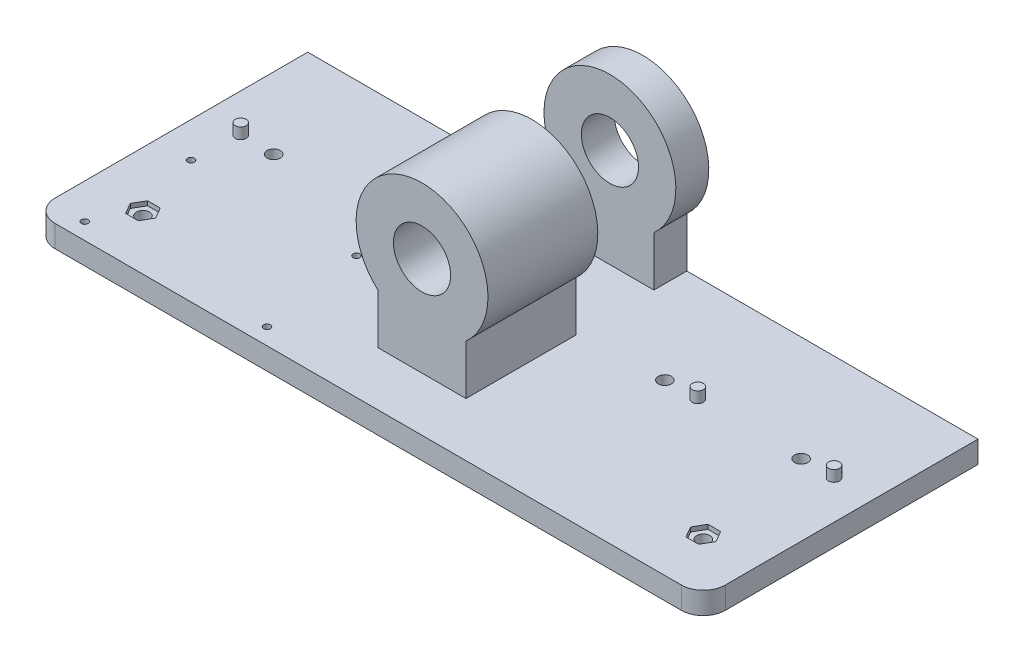
SolidWorks part; units mm, degrees
ref_plane "Front Plane" through (0, 0, 0) normal (0, 0, 1) x (1, 0, 0)
ref_plane "Top Plane" through (0, 0, 0) normal (0, 1, 0) x (1, 0, 0)
ref_plane "Right Plane" through (0, 0, 0) normal (1, 0, 0) x (0, 0, -1)
sketch "Sketch1" plane through (0, 0, 0) normal (0, 1, 0) x (1, 0, 0)
  line L0 (152.5, 125) -> (152.5, 0) construction
  line L1 (0, 0) -> (305, 0)
  line L2 (0, 0) -> (0, 125)
  line L3 (0, 125) -> (305, 125)
  line L4 (305, 0) -> (305, 125)
  line L5 (25, 100) -> (280, 100) construction
  line L6 (280, 25) -> (280, 100) construction
  line L7 (25, 25) -> (280, 25) construction
  line L8 (25, 25) -> (25, 100) construction
  line L9 (152.5, 62.5) -> (25, 62.5) construction
  line L10 (30.7735, 100) -> (27.8868, 105) construction
  line L11 (27.8868, 105) -> (22.1132, 105) construction
  line L12 (22.1132, 105) -> (19.2265, 100) construction
  line L13 (19.2265, 100) -> (22.1132, 95) construction
  line L14 (22.1132, 95) -> (27.8868, 95) construction
  line L15 (27.8868, 95) -> (30.7735, 100) construction
  line L16 (27.8868, 30) -> (30.7735, 25) construction
  line L17 (22.1132, 30) -> (27.8868, 30) construction
  line L18 (19.2265, 25) -> (22.1132, 30) construction
  line L19 (22.1132, 20) -> (19.2265, 25) construction
  line L20 (27.8868, 20) -> (22.1132, 20) construction
  line L21 (30.7735, 25) -> (27.8868, 20) construction
  line L22 (282.8868, 30) -> (277.1132, 30) construction
  line L23 (285.7735, 25) -> (282.8868, 30) construction
  line L24 (282.8868, 20) -> (285.7735, 25) construction
  line L25 (277.1132, 20) -> (282.8868, 20) construction
  line L26 (274.2265, 25) -> (277.1132, 20) construction
  line L27 (277.1132, 30) -> (274.2265, 25) construction
  line L28 (277.1132, 95) -> (274.2265, 100) construction
  line L29 (282.8868, 95) -> (277.1132, 95) construction
  line L30 (285.7735, 100) -> (282.8868, 95) construction
  line L31 (282.8868, 105) -> (285.7735, 100) construction
  line L32 (277.1132, 105) -> (282.8868, 105) construction
  line L33 (274.2265, 100) -> (277.1132, 105) construction
  line L34 (172.5, 75) -> (172.5, 125) construction
  line L35 (132.5, 0) -> (172.5, 0) construction
  line L36 (132.5, 0) -> (132.5, 125) construction
  line L37 (132.5, 125) -> (172.5, 125) construction
  line L38 (172.5, 0) -> (172.5, 125) construction
  line L40 (132.5, 75) -> (132.5, 25) construction
  line L41 (132.5, 25) -> (172.5, 25) construction
  line L42 (172.5, 75) -> (172.5, 25) construction
  line L50 (305, 14.5) -> (253.3, 14.5) construction
  line L51 (10, 69.5) -> (10, 84.5) construction
  line L52 (10, 69.5) -> (40, 69.5) construction
  line L53 (10, 84.5) -> (25, 69.5) construction
  line L54 (0, 125) -> (108, 125) construction
  line L55 (0, 125) -> (0, 84.5) construction
  line L56 (0, 84.5) -> (108, 84.5) construction
  line L57 (108, 125) -> (108, 84.5) construction
  line L58 (25, 69.5) -> (25, 84.5) construction
  line L59 (40, 84.5) -> (0, 84.5) construction
  line L60 (40, 84.5) -> (40, 69.5) construction
  line L62 (0, 84.5) -> (0, 69.5) construction
  line L63 (102, 84.5) -> (102, 69.5) construction
  line L64 (62, 0) -> (62, 125) construction
  line L65 (253.3, 14.5) -> (253.3, 0) construction
  line L67 (253.3, 14.5) -> (280.2, 14.5) construction
  circle A1 centre (25, 100) radius 5 construction
  circle A3 centre (280, 25) radius 3
  circle A4 centre (25, 25) radius 3
  circle A10 centre (17.5, 77) radius 3 construction
  circle A11 centre (32.5, 77) radius 3
  circle A12 centre (79.5, 77) radius 3 construction
  circle A13 centre (94.5, 77) radius 3
  circle A14 centre (210.5, 77) radius 3
  circle A15 centre (225.5, 77) radius 3 construction
  circle A16 centre (272.5, 77) radius 3
  circle A17 centre (287.5, 77) radius 3 construction
  point P54 (25, 69.5)
  point P56 (0, 0)
  point P57 (17.5, 77)
  dimension "D3" = 6
  dimension "D1" = 305
  dimension "D2" = 125
  dimension "D5" = 10
  dimension "D6" = 40
  dimension "D7" = 40.5
  dimension "D9" = 108
  dimension "D15" = 62
  dimension "D18" = 51.7
  dimension "D19" = 14.5
  dimension "D20" = 26.9
  dimension "D8" = 40
  dimension "D11" = 30
  dimension "D10" = 15
  dimension "D4" = 25
  dimension "D14" = 2
extrude "Boss-Extrude1" add sketch "Sketch1" along normal blind 10
sketch "Sketch7" plane through (0, 10, 0) normal (0, 1, 0) x (1, 0, 0)
  line L0 (0, 0) -> (305, 0) construction
  line L1 (132.5, 24.5) -> (172.5, 24.5)
  line L2 (132.5, 24.5) -> (132.5, 74.5)
  line L3 (132.5, 74.5) -> (172.5, 74.5)
  line L4 (172.5, 24.5) -> (172.5, 74.5)
  line L5 (152.5, 0) -> (152.5, 125) construction
  line L6 (305, 125) -> (0, 125) construction
  line L18 (132.5, 110) -> (172.5, 110)
  line L19 (132.5, 110) -> (132.5, 125)
  line L20 (132.5, 125) -> (172.5, 125)
  line L21 (172.5, 110) -> (172.5, 125)
  point P11 (152.5, 74.5)
  point P20 (152.5, 110)
  dimension "D1" = 40
  dimension "D2" = 50
  dimension "D4" = 15
  dimension "D3" = 35.5
extrude "Boss-Extrude2" add sketch "Sketch7" along normal blind 22.6393
sketch "Sketch11" plane through (0, 0, -24.5) normal (0, 0, 1) x (1, 0, 0)
  circle A0 centre (152.5, 55) radius 30
  circle A1 centre (152.5, 55) radius 13
  dimension "D1" = 60
  dimension "D2" = 26
extrude "Boss-Extrude3" add sketch "Sketch11" against normal up to surface (100.5 mm away) up to face at (152.5, 13.1598, -125)
ref_plane "Plane1" through (0, 0, -62.5) normal (0, 0, 1) x (1, 0, 0)
sketch "Sketch12" plane through (305, 0, 0) normal (1, 0, 0) x (0, 0, -1)
  line L0 (125, 85) -> (24.5, 85) construction
  line L1 (74.5, 10) -> (110, 10)
  line L2 (74.5, 10) -> (74.5, 85)
  line L3 (74.5, 85) -> (110, 85)
  line L4 (110, 10) -> (110, 85)
  line L6 (110, 32.6393) -> (110, 10) construction
extrude "Cut-Extrude2" cut sketch "Sketch12" against normal through all
sketch "Sketch6" plane through (0, 10, 0) normal (0, 1, 0) x (1, 0, 0)
  line L0 (152.5, 125) -> (152.5, 0) construction
  line L8 (0, 0) -> (305, 0) construction
  line L9 (152.5, 62.5) -> (0, 62.5) construction
  line L10 (0, 125) -> (0, 0) construction
  line L29 (27.8868, 30) -> (30.7735, 25)
  line L30 (274.2265, 25) -> (277.1132, 20)
  line L31 (277.1132, 20) -> (282.8868, 20)
  line L32 (282.8868, 20) -> (285.7735, 25)
  line L33 (285.7735, 25) -> (282.8868, 30)
  line L34 (282.8868, 30) -> (277.1132, 30)
  line L35 (277.1132, 30) -> (274.2265, 25)
  line L36 (22.1132, 30) -> (27.8868, 30)
  line L37 (19.2265, 25) -> (22.1132, 30)
  line L38 (22.1132, 20) -> (19.2265, 25)
  line L39 (27.8868, 20) -> (22.1132, 20)
  line L40 (30.7735, 25) -> (27.8868, 20)
  circle A0 centre (280, 25) radius 5 construction
  dimension "D1" = 10
extrude "Cut-Extrude1" cut sketch "Sketch6" against normal blind 2
sketch "Sketch15" plane through (0, 10, 0) normal (0, 1, 0) x (1, 0, 0)
  line L0 (79.5, 77) -> (17.5, 77) construction
  line L1 (48.5, 77) -> (48.5, 84.5) construction
  line L2 (0, 84.5) -> (108, 84.5) construction
  line L3 (152.5, 125) -> (152.5, 0) construction
  circle A1 centre (79.5, 77) radius 2.5
  circle A2 centre (17.5, 77) radius 2.5
  circle A3 centre (17.5, 77) radius 2.5
  circle A4 centre (225.5, 77) radius 2.5
  circle A5 centre (287.5, 77) radius 2.5
  dimension "D1" = 0.5
extrude "Boss-Extrude5" add sketch "Sketch15" along normal blind 5
sketch "Sketch16" plane through (0, 10, 0) normal (0, 1, 0) x (1, 0, 0)
  line L0 (0, 0) -> (305, 0) construction
  line L1 (0, 125) -> (0, 0) construction
  circle A0 centre (16, 7.5) radius 1.55
  circle A1 centre (98.95, 7.5) radius 1.55
  circle A2 centre (16, 55.866) radius 1.55
  circle A3 centre (91.33, 55.866) radius 1.55
  dimension "D1" = 3.1
  dimension "D2" = 7.5
  dimension "D3" = 82.95
  dimension "D4" = 16
  dimension "D5" = 48.366
  dimension "D6" = 75.33
extrude "Cut-Extrude3" cut sketch "Sketch16" against normal through all
chamfer "Chamfer1" distance 3.3 angle 45 4 edges at (272.5, 0, -74) (210.5, 0, -74) (94.5, 0, -80) (32.5, 0, -80)
fillet "Fillet3" radius 10 2 edges at (305, 5, 0) (0, 5, 0)
fillet "Fillet2" [suppressed] radius 0.5
chamfer "Chamfer2" distance 1.65 4 edges at (98.95, 0, -5.95) (91.33, 0, -54.316) (16, 0, -5.95) (16, 0, -54.316)
equation "\"joint_width\"=4"
equation "\"short_base_length\"=12.5"
equation "\"D2@Sketch1\"=\"short_base_length\""
equation "\"outer_diam_main_joint\"=6"
equation "\"D1@Sketch11\"=\"outer_diam_main_joint\""
equation "\"D1@Sketch7\"=\"outer_diam_main_joint\"-2"
equation "\"D1@Boss-Extrude2\"=(\"outer_diam_main_joint\"/2)+1.5cm-sqr((\"outer_diam_main_joint\"/2)^2-((\"outer_diam_main_joint\"-2)/2)^2)"
equation "\"D6@Sketch1\"=\"outer_diam_main_joint\"-2"
equation "\"pulleyside\"=1.5"
